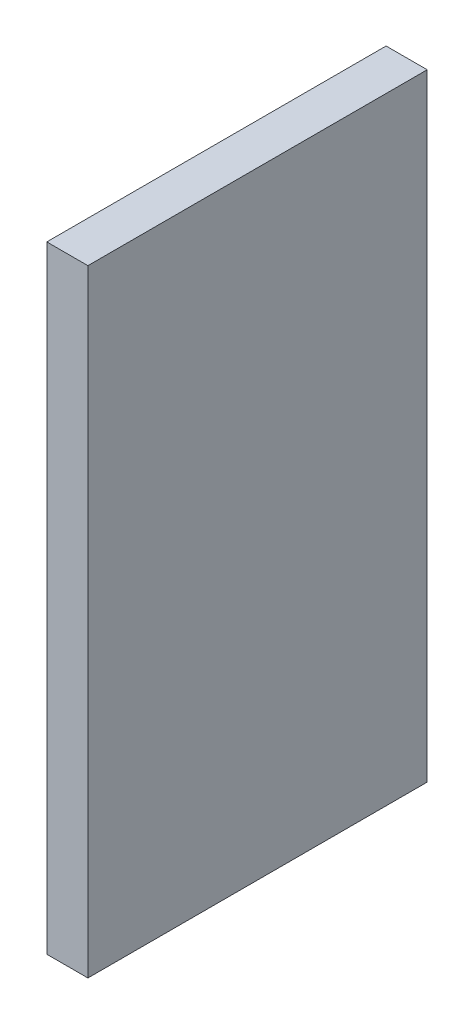
SolidWorks part; units mm, degrees
ref_plane "Front Plane" through (0, 0, 0) normal (0, 0, 1) x (1, 0, 0)
ref_plane "Top Plane" through (0, 0, 0) normal (0, 1, 0) x (1, 0, 0)
ref_plane "Right Plane" through (0, 0, 0) normal (1, 0, 0) x (0, 0, -1)
sketch "Sketch1" plane through (0, 0, 0) normal (0, 1, 0) x (1, 0, 0)
  line L1 (0, 0) -> (4, 0)
  line L2 (0, 0) -> (0, 33)
  line L3 (0, 33) -> (4, 33)
  line L4 (4, 0) -> (4, 33)
  dimension "D1" = 33
  dimension "D2" = 4
extrude "Boss-Extrude1" add sketch "Sketch1" along normal blind 60 contours L4 L3 L2 L1
